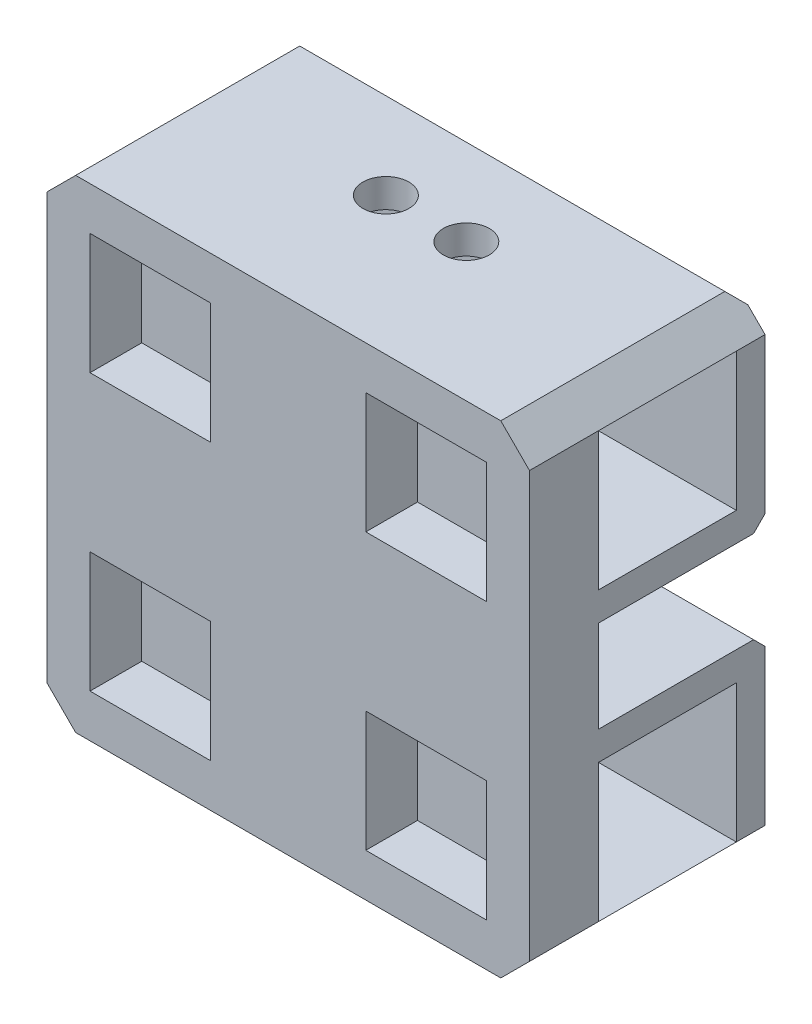
SolidWorks part; units mm, degrees
ref_plane "Plan de face" through (0, 0, 0) normal (0, 0, 1) x (1, 0, 0)
ref_plane "Plan de dessus" through (0, 0, 0) normal (0, 1, 0) x (1, 0, 0)
ref_plane "Plan de droite" through (0, 0, 0) normal (1, 0, 0) x (0, 0, -1)
sketch "Esquisse1" plane through (0, 0, 0) normal (0, 0, 1) x (1, 0, 0)
  line L0 (0, -49.5) -> (0, -41.5)
  line L1 (0, 0) -> (42, 0)
  line L2 (0, 0) -> (0, -42)
  line L3 (0, -42) -> (42, -42)
  line L4 (42, 0) -> (42, -42)
  line L6 (42, 0) -> (42, -42)
  line L7 (42, -10.5) -> (42, -18.5)
  line L11 (0, -10.5) -> (0, -18.5)
  line L15 (42, -41.5) -> (42, -49.5)
  line L19 (0, -41.5) -> (0, -49.5)
  line L22 (0, -18.5) -> (0, -10.5)
  line L23 (42, -10.5) -> (42, -18.5)
  line L24 (42, -41.5) -> (42, -49.5)
  line L25 (42, -49.5) -> (42.1497, -49.6465)
  dimension "D4" = 42
  dimension "D5" = 42
extrude "Boss.-Extru.1" add sketch "Esquisse1" along normal blind 6 contours L4 L1 L2 L3 | L4 | L4 | L4 | L0 | L2 region at (21, -21, 0)
sketch "Esquisse2" plane through (0, 0, 0) normal (0, 0, -1) x (-1, 0, 0)
  line L0 (0, -42) -> (-42, -42) construction
  line L1 (0, -42) -> (-42, -42)
  line L2 (0, -42) -> (0, -25)
  line L3 (0, -25) -> (-42, -25)
  line L4 (-42, -42) -> (-42, -25)
  line L5 (0, 0) -> (0, -42) construction
  line L6 (-42, 0) -> (-42, -42) construction
  line L8 (-42, 0) -> (-42, -42) construction
  point P6 (-42, -21)
  point P8 (-42, -33.5)
  dimension "D1" = 17
  dimension "D2" = 12.5
  dimension "D4" = 0
  dimension "D5" = 0
  dimension "D6" = 8.5
extrude "Boss.-Extru.3" add sketch "Esquisse2" along normal blind 14.5
sketch "Esquisse3" plane through (42, 0, 0) normal (1, 0, 0) x (0, 0, -1)
  line L0 (0, 0) -> (0, -25) construction
  line L1 (12, -39.5) -> (0, -39.5)
  line L2 (12, -39.5) -> (12, -27.5)
  line L3 (12, -27.5) -> (0, -27.5)
  line L4 (0, -39.5) -> (0, -27.5)
  line L5 (14.5, -42) -> (-6, -42) construction
  dimension "D1" = 12
  dimension "D2" = 12
  dimension "D3" = 0
  dimension "D4" = 2.5
extrude "Enlèv. mat.-Extru.3" cut sketch "Esquisse3" against normal through all
ref_plane "Plan1" through (0, -21, 0) normal (0, -1, 0) x (-1, 0, 0)
mirror "Symétrie1" about plane through (0, -21, 0) normal (0, -1, 0) of "Boss.-Extru.3", "Enlèv. mat.-Extru.3"
sketch "Esquisse4" plane through (0, -42, 0) normal (0, -1, 0) x (1, 0, 0)
  line L1 (0, -12) -> (42, -12) construction
  line L2 (42, -14.5) -> (0, -14.5) construction
  circle A0 centre (24.5, -6) radius 2
  circle A1 centre (17.5, -6) radius 2
  point P10 (21, -14.5)
  dimension "D1" = 6
  dimension "D3" = 4
  dimension "D4" = 4
  dimension "D2" = 3.5
  dimension "D5" = 7
  dimension "D6" = 8.5
extrude "Enlèv. mat.-Extru.4" cut sketch "Esquisse4" against normal blind 42
chamfer "Chanfrein1" distance 2.5 angle 45 4 edges at (0, 0, -4.25) (0, -42, -4.25) (42, -42, -4.25) (42, 0, -4.25)
sketch "Esquisse5" plane through (0, 0, 6) normal (0, 0, 1) x (1, 0, 0)
  line L1 (3.75, -3.75) -> (14.25, -3.75)
  line L2 (3.75, -3.75) -> (3.75, -14.25)
  line L3 (3.75, -14.25) -> (14.25, -14.25)
  line L4 (14.25, -3.75) -> (14.25, -14.25)
  line L5 (-3.3, -21) -> (3.3, -21) construction
  line L6 (2.5, 0) -> (39.5, 0) construction
  point P4 (14.25, -9)
  point P9 (21, 0)
  point P10 (9, -14.25)
  dimension "D1" = 10.5
  dimension "D2" = 10.5
  dimension "D3" = 12
  dimension "D4" = 12
extrude "Enlèv. mat.-Extru.5" cut sketch "Esquisse5" against normal blind 4.5
ref_plane "Plan2" through (21, 0, 0) normal (-1, 0, 0) x (0, 0, 1)
mirror "Symétrie2" about plane through (21, 0, 0) normal (-1, 0, 0) of "Enlèv. mat.-Extru.5"
mirror "Symétrie3" about plane through (0, -21, 0) normal (0, -1, 0) of "Symétrie2", "Enlèv. mat.-Extru.5"
chamfer "Chanfrein2" distance 1 angle 45 4 edges at (21, -17, -14.5) (21, -25, -14.5) (21, 0, -14.5) (21, -42, -14.5)
equation "\"é\"=1.5583"
equation "\"à\"=2.55842"
